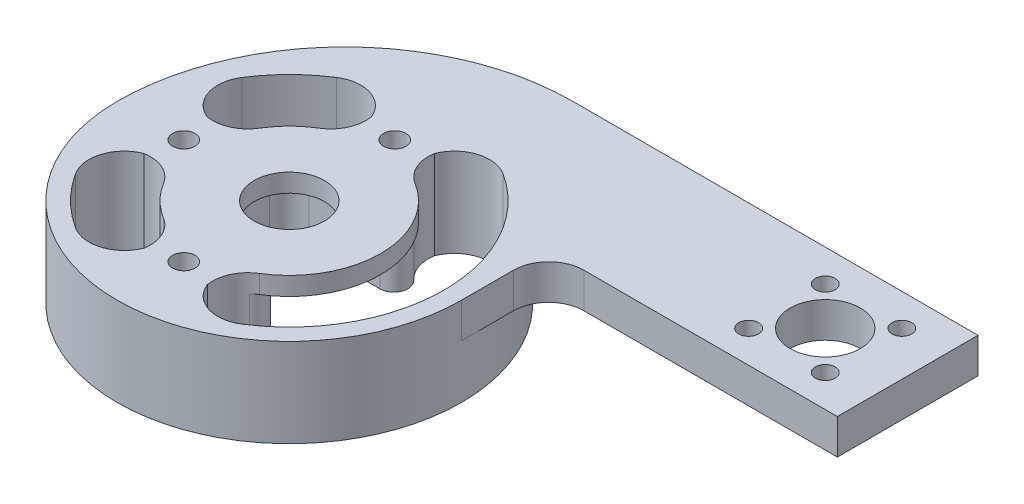
SolidWorks part; units mm, degrees
material "6061-T6 (SS)"
ref_plane "Front Plane" through (0, 0, 0) normal (0, 0, 1) x (1, 0, 0)
ref_plane "Top Plane" through (0, 0, 0) normal (0, 1, 0) x (1, 0, 0)
ref_plane "Right Plane" through (0, 0, 0) normal (1, 0, 0) x (0, 0, -1)
sketch "Sketch1" plane through (0, 0, 0) normal (0, 1, 0) x (1, 0, 0)
  line L0 (-1.1049, 0) -> (-31.0896, 0) construction
  line L1 (-1.1049, 0) -> (31.0896, 0) construction
  circle A0 centre (0, 0) radius 31.0896
  dimension "D1" = 62.1792
extrude "Boss-Extrude1" add sketch "Sketch1" along normal blind 16.002
sketch "Sketch2" plane through (0, 16.002, 0) normal (0, 1, 0) x (1, 0, 0)
  line L0 (0, 0) -> (-31.0896, 0) construction
  line L1 (0, 0) -> (31.0896, 0) construction
  line L2 (-31.0896, 0) -> (-31.0896, 41.148)
  line L3 (-31.0896, 41.148) -> (83.2104, 41.148)
  line L4 (83.2104, 41.148) -> (83.2104, 15.748)
  line L5 (31.0896, 0) -> (31.0896, 15.748)
  line L6 (31.0896, 15.748) -> (83.2104, 15.748)
  circle A0 centre (0, 0) radius 31.0896 construction
  circle A2 centre (0, 0) radius 31.0896
  arc A3 (-31.0896, 0) -> (31.0896, 0) centre (0, 0) ccw
  dimension "D1" = 0
  dimension "D2" = 114.3
  dimension "D3" = 25.4
  dimension "D4" = 15.748
extrude "Boss-Extrude2" add sketch "Sketch2" against normal blind 6.35
fillet "Fillet1" [suppressed] radius 6.35
fillet "Fillet2" radius 6.35 1 edges at (31.0896, 12.827, -15.748)
sketch "Sketch4" plane through (0, 16.002, 0) normal (0, 1, 0) x (1, 0, 0)
  line L0 (83.2104, 41.148) -> (58.166, 41.148) construction
  line L1 (83.2104, 41.148) -> (-31.0896, 41.148) construction
  line L2 (58.166, 41.148) -> (58.166, 28.448) construction
  line L3 (58.166, 28.448) -> (78.486, 28.448) construction
  line L4 (68.326, 28.448) -> (75.2408, 35.3628) construction
  line L5 (68.326, 28.448) -> (75.2408, 21.5332) construction
  line L6 (68.326, 28.448) -> (61.4112, 21.5332) construction
  line L7 (68.326, 28.448) -> (61.4112, 35.3628) construction
  circle A0 centre (61.4112, 35.3628) radius 1.778
  circle A1 centre (75.2408, 35.3628) radius 1.778
  circle A2 centre (75.2408, 21.5332) radius 1.778
  circle A3 centre (68.326, 28.448) radius 6.35
  circle A4 centre (61.4112, 21.5332) radius 1.778
extrude "Cut-Extrude2" cut sketch "Sketch4" against normal up to next
sketch "Sketch7" plane through (0, 0, 0) normal (0, 1, 0) x (1, 0, 0)
  line L0 (0, 27.94) -> (0, -31.0896)
  line L1 (0, 0) -> (-7.4507, 26.9283)
  line L2 (-7.4507, -26.9283) -> (0, 0)
  line L3 (0, 0) -> (7.4507, 26.9283)
  line L4 (0, 0) -> (7.4507, -26.9283)
  line L5 (-26.9283, 7.4507) -> (0, 0)
  line L6 (0, 0) -> (26.9283, -7.4507) construction
  line L7 (-26.9283, -7.4507) -> (0, 0)
  line L8 (0, 0) -> (26.9283, 7.4507) construction
  line L9 (0, 0) -> (-26.2234, 0) construction
  circle A0 centre (0, 0) radius 16.51
  circle A1 centre (0, 0) radius 27.94
  circle A2 centre (0, 0) radius 31.0896 construction
  circle A3 centre (-19.05, 0) radius 2.0193
  circle A4 centre (0, 19.05) radius 2.0193
  circle A5 centre (0, -19.05) radius 2.0193
  circle A6 centre (0, 0) radius 19.05 construction
  dimension "D1" = 33.02
  dimension "D2" = 55.88
  dimension "D3" = 4.0386
  dimension "D4" = 38.1
  dimension "D5" = 5.08
  dimension "D6" = 5.08
  dimension "D7" = 5.08
  dimension "D8" = 5.08
extrude "Cut-Extrude4" cut sketch "Sketch7" along normal through all contours L4 A1 L3 A0 | L7 A1 L2 A0 | L1 A1 L5 A0 | A3 | A5 | A4 region at (16.8291, 0, 0) region at (-15.3599, 0, -15.3599) region at (-15.3599, 0, 15.3599)
fillet "Fillet7" radius 6.35 12 edges at (-26.9283, 8.001, -7.4507) (-7.4507, 8.001, -26.9283) (-4.4027, 8.001, -15.9122) (4.4027, 8.001, -15.9122) (7.4507, 8.001, -26.9283) (4.4027, 8.001, 15.9122) (7.4507, 8.001, 26.9283) (-7.4507, 8.001, 26.9283) (-4.4027, 8.001, 15.9122) (-15.9122, 8.001, 4.4027) (-26.9283, 8.001, 7.4507) (-15.9122, 8.001, -4.4027)
fillet "Fillet8" radius 41.148 1 edges at (-31.0896, 12.827, -41.148)
sketch "Sketch8" plane through (0, 0, 0) normal (0, -1, 0) x (1, 0, 0)
  line L0 (-10.414, 10.414) -> (10.414, 10.414)
  line L1 (10.414, 10.414) -> (10.414, -10.414) construction
  line L2 (10.414, -10.414) -> (-10.414, -10.414)
  line L3 (-10.414, -10.414) -> (-10.414, 10.414)
  line L4 (10.414, 10.414) -> (-10.414, -10.414) construction
  line L5 (-10.414, 10.414) -> (10.414, -10.414) construction
  arc A0 (10.414, 10.414) -> (10.414, -10.414) centre (10.414, 0) cw
  dimension "D2" = 10.414
  dimension "D1" = 20.828
extrude "Cut-Extrude5" cut sketch "Sketch8" against normal blind 12.7
fillet "Fillet9" radius 2.54 2 edges at (13.0872, 6.35, 10.0651) (13.0872, 6.35, -10.0651)
sketch "Sketch9" plane through (0, 12.7, 0) normal (0, -1, 0) x (1, 0, 0)
  circle A0 centre (0, 0) radius 6.35
  dimension "D1" = 12.7
extrude "Cut-Extrude6" cut sketch "Sketch9" against normal up to surface (3.302 mm away) up to face at (0, 16.002, 21.0693)
fillet "Fillet10" radius 3.556 2 edges at (-10.414, 6.35, 10.414) (-10.414, 6.35, -10.414)
